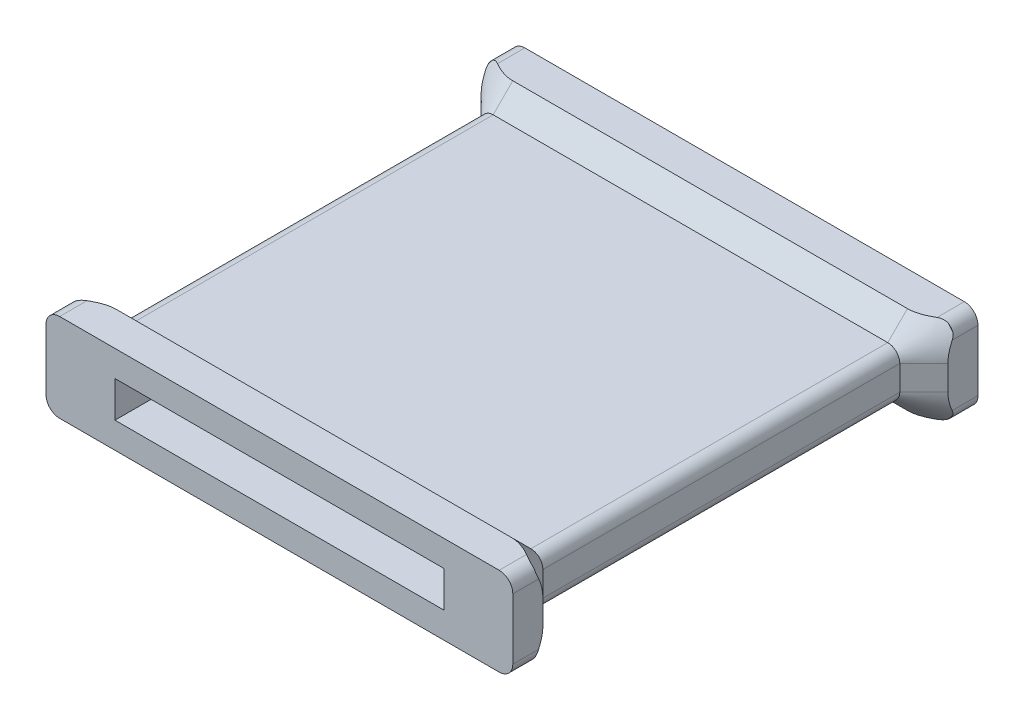
SolidWorks part; units mm, degrees
ref_plane "Front Plane" through (0, 0, 0) normal (0, 0, 1) x (1, 0, 0)
ref_plane "Top Plane" through (0, 0, 0) normal (0, 1, 0) x (1, 0, 0)
ref_plane "Right Plane" through (0, 0, 0) normal (1, 0, 0) x (0, 0, -1)
sketch "Sketch1" plane through (0, 0, 0) normal (0, 0, 1) x (1, 0, 0)
  line L1 (-20.5, 2.25) -> (20.5, 2.25)
  line L2 (-20.5, 2.25) -> (-20.5, -2.25)
  line L3 (-20.5, -2.25) -> (20.5, -2.25)
  line L4 (20.5, 2.25) -> (20.5, -2.25)
  line L5 (-20.5, 2.25) -> (20.5, -2.25) construction
  line L6 (-20.5, -2.25) -> (20.5, 2.25) construction
  line L7 (-29.1, 5.5) -> (29.1, 5.5)
  line L8 (-29.1, 5.5) -> (-29.1, -5.5)
  line L9 (-29.1, -5.5) -> (29.1, -5.5)
  line L10 (29.1, 5.5) -> (29.1, -5.5)
  line L11 (-29.1, 5.5) -> (29.1, -5.5) construction
  line L12 (-29.1, -5.5) -> (29.1, 5.5) construction
  point P0 (0, 0)
  point P6 (0, 0)
  dimension "D1" = 41
  dimension "D2" = 4.5
  dimension "D3" = 11
  dimension "D4" = 58.2
extrude "Boss-Extrude1" add sketch "Sketch1" along normal blind 58
sketch "Sketch2" plane through (0, 0, 58) normal (0, 0, 1) x (1, 0, 0)
  line L0 (20.5, 2.25) -> (-20.5, 2.25) construction
  line L1 (-26.1, 3.05) -> (26.1, 3.05)
  line L2 (-26.1, 3.05) -> (-26.1, -3.05)
  line L3 (-26.1, -3.05) -> (26.1, -3.05)
  line L4 (26.1, 3.05) -> (26.1, -3.05)
  line L5 (-26.1, 3.05) -> (26.1, -3.05) construction
  line L6 (-26.1, -3.05) -> (26.1, 3.05) construction
  line L7 (-29.1, 5.5) -> (-29.1, -5.5) construction
  point P0 (0, 0)
  dimension "D1" = 0.8
  dimension "D2" = 3
extrude "Cut-Extrude1" cut sketch "Sketch2" against normal offset from surface (52 mm away) 3 from offset 3 flip side to cut up to face at (0, 0, 0) offset against normal yes
fillet "Fillet1" radius 1.5 4 edges at (26.1, -3.05, 29) (26.1, 3.05, 29) (-26.1, -3.05, 29) (-26.1, 3.05, 29)
fillet "Fillet2" radius 1.7 8 edges at (29.1, -5.5, 1.5) (29.1, 5.5, 1.5) (29.1, -5.5, 56.5) (29.1, 5.5, 56.5) (-29.1, -5.5, 56.5) (-29.1, 5.5, 56.5) (-29.1, -5.5, 1.5) (-29.1, 5.5, 1.5)
chamfer "Chamfer1" distance 3.75 angle 45 16 edges at (0, -3.05, 3) (-25.6607, -2.6107, 3) (25.6607, -2.6107, 3) (-26.1, 0, 3) (26.1, 0, 3) (-25.6607, 2.6107, 3) (25.6607, 2.6107, 3) (0, 3.05, 3) (0, -3.05, 55) (25.6607, -2.6107, 55) (-25.6607, -2.6107, 55) (26.1, 0, 55) (-26.1, 0, 55) (25.6607, 2.6107, 55) (-25.6607, 2.6107, 55) (0, 3.05, 55)
sketch "Sketch5" plane through (0, -2.25, 0) normal (0, 1, 0) x (1, 0, 0)
  line L0 (-20.5, -52) -> (-20.5, -6)
  line L1 (-20.5, -58) -> (-20.5, 0) construction
  line L2 (-20.5, -58) -> (-20.5, 0) construction
  line L3 (-21, -8.2462) -> (-21, -45.0079) construction
  line L4 (27.4, 0) -> (-27.4, 0) construction
  line L5 (27.4, -58) -> (-27.4, -58) construction
  arc A0 (-20.5, -6) -> (-20.5, -52) centre (508.25, -29) ccw
  dimension "D1" = 1
  dimension "D2" = 6
  dimension "D3" = 6
extrude "Cut-Extrude3" cut sketch "Sketch5" along normal up to surface (4.5 mm away) up to face at (0, 2.25, 29)
